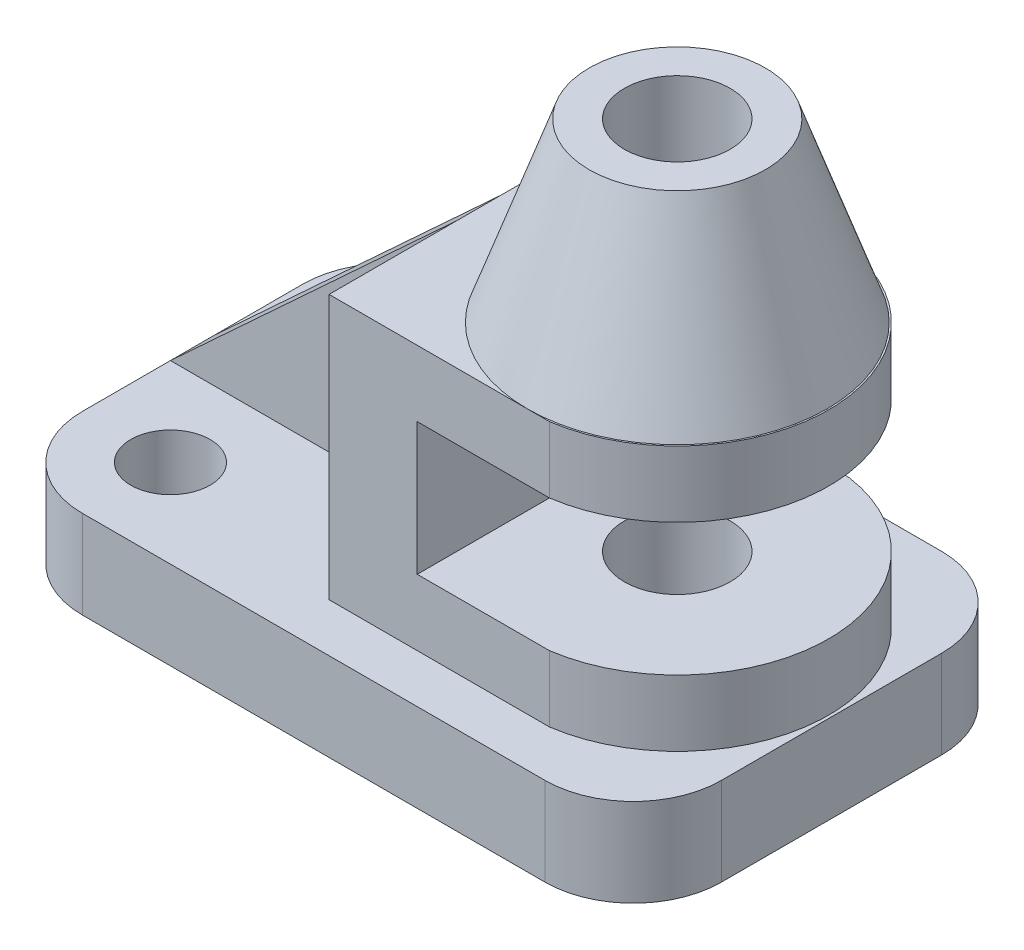
SolidWorks part; units mm, degrees
ref_plane "Front Plane" through (0, 0, 0) normal (0, 0, 1) x (1, 0, 0)
ref_plane "Top Plane" through (0, 0, 0) normal (0, 1, 0) x (1, 0, 0)
ref_plane "Right Plane" through (0, 0, 0) normal (1, 0, 0) x (0, 0, -1)
sketch "Sketch1" plane through (0, 0, 0) normal (0, 1, 0) x (1, 0, 0)
  line L1 (52.5, 45) -> (-52.5, 45)
  line L2 (72.5, 25) -> (72.5, -25)
  line L3 (52.5, -45) -> (-52.5, -45)
  line L4 (-72.5, 25) -> (-72.5, -25)
  line L6 (72.5, -45) -> (65.187, -40.4609) construction
  arc A0 (72.5, -25) -> (52.5, -45) centre (52.5, -25) cw
  arc A1 (72.5, 25) -> (52.5, 45) centre (52.5, 25) ccw
  arc A2 (-52.5, -45) -> (-72.5, -25) centre (-52.5, -25) cw
  arc A3 (-52.5, 45) -> (-72.5, 25) centre (-52.5, 25) ccw
  circle A4 centre (-52.5, 25) radius 9
  circle A5 centre (-52.5, -25) radius 9
  point P0 (0, 0)
  dimension "D3" = 20
  dimension "D1" = 18
  dimension "D2" = 18
  dimension "D4" = 50
extrude "Boss-Extrude1" add sketch "Sketch1" along normal blind 20
sketch "Sketch2" plane through (0, 20, 0) normal (0, 1, 0) x (1, 0, 0)
  line L0 (-52.8167, 25) -> (-52.8167, -25) construction
  line L1 (-7.3131, 0) -> (-98.3202, 0) construction
  line L2 (-7.5, 34) -> (-7.5, -44.041) construction
  line L4 (-72.5, 25) -> (-72.5, -25) construction
  line L5 (-7.5, 34) -> (12.5, 34)
  line L7 (-7.5, 34) -> (-7.5, -34)
  line L8 (-7.5, -34) -> (12.5, -34)
  line L9 (12.5, 34) -> (12.5, -34)
  line L13 (-7.5, 0) -> (-7.5, 3.8704)
  line L14 (52.5, 45) -> (-52.5, 45) construction
  point P8 (0, 0)
  point P13 (-52.8167, 0)
  dimension "D1" = 11
  dimension "D2" = 65
  dimension "D3" = 68
  dimension "D4" = 20
extrude "Boss-Extrude5" add sketch "Sketch2" along normal blind 60 contours L9 L5 L7 L8 region at (2.5, 20, 0)
sketch "Sketch7" plane through (0, 20, 0) normal (0, 1, 0) x (1, 0, 0)
  line L0 (-52.5, -45) -> (52.5, -45) construction
  line L1 (12.5, -34) -> (42.5, -34)
  line L2 (12.5, -34) -> (12.5, 34)
  line L5 (12.5, 34) -> (42.5, 34)
  arc A2 (42.5, 34) -> (42.5, -34) centre (37.5, 0) cw
  point P1 (12.5, 34)
  dimension "D1" = 11
  dimension "D2" = 30
  dimension "D3" = 30
extrude "Boss-Extrude8" add sketch "Sketch7" along normal blind 60
sketch "Sketch23" plane through (0, 80, 0) normal (0, 1, 0) x (1, 0, 0)
  circle A1 centre (37.5, 0) radius 34
ref_plane "Plane1" through (0, 120, 0) normal (0, 1, 0) x (1, 0, 0)
sketch "Sketch24" plane through (0, 120, 0) normal (0, 1, 0) x (1, 0, 0)
  circle A0 centre (37.5, 0) radius 20
  dimension "D1" = 40
loft "Loft1" add profiles "Sketch23", "Sketch24" connector at (6.1705, 80, 13.2083) connector at (20.185, 120, 10.0096)
sketch "Sketch25" plane through (0, 120, 0) normal (0, 1, 0) x (1, 0, 0)
  circle A0 centre (37.5, 0) radius 12
extrude "Cut-Extrude12" cut sketch "Sketch25" against normal through all
extrude "Cut-Extrude13" cut sketch "Sketch7<2>" along normal blind 30 from offset 15
sketch "Sketch7<2>" plane through (0, 20, 0) normal (0, 1, 0) x (1, 0, 0) same geometry as "Sketch7"
sketch "Sketch27" plane through (0, 0, 0) normal (0, 0, 1) x (1, 0, 0)
  line L0 (-7.5, 80) -> (-7.5, 20)
  line L1 (-7.5, 20) -> (-72.5, 20)
  line L2 (-72.5, 20) -> (-7.5, 80)
extrude "Boss-Extrude9" add sketch "Sketch27" along normal mid plane 10
sketch "Sketch20" plane through (0, 80, 0) normal (0, 1, 0) x (1, 0, 0)
